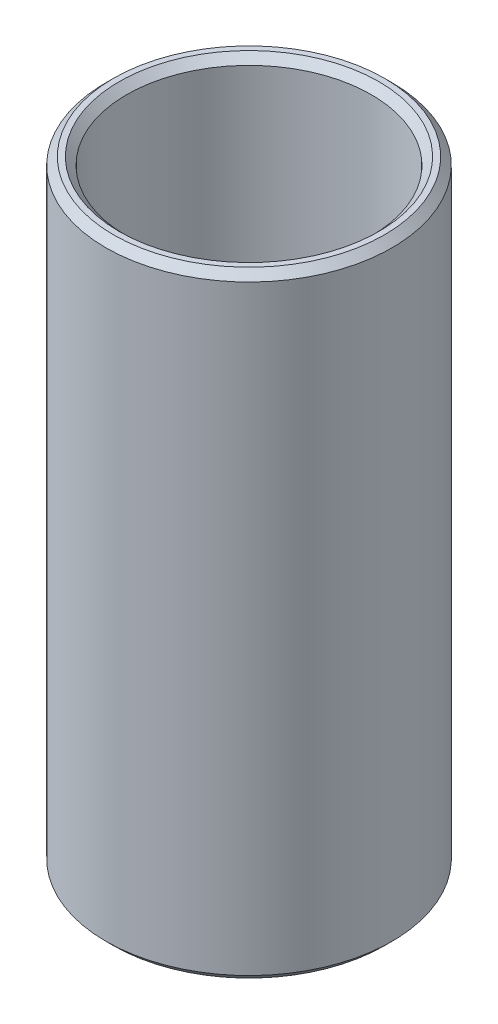
SolidWorks part; units mm, degrees
ref_plane "Front Plane" through (0, 0, 0) normal (0, 0, 1) x (1, 0, 0)
ref_plane "Top Plane" through (0, 0, 0) normal (0, 1, 0) x (1, 0, 0)
ref_plane "Right Plane" through (0, 0, 0) normal (1, 0, 0) x (0, 0, -1)
sketch "Sketch1" plane through (0, 0, 0) normal (0, 1, 0) x (1, 0, 0)
  circle A0 centre (0, 0) radius 57.5
  dimension "SLEEVE_OD" = 115
extrude "Boss-Extrude1" add sketch "Sketch1" along normal blind 247.4371
sketch "Sketch2" plane through (0, 0, 0) normal (0, 1, 0) x (1, 0, 0)
  circle A0 centre (0, 0) radius 49.1676
  dimension "BORE_D" = 98.3353
extrude "Cut-Extrude1" cut sketch "Sketch2" along normal through all
chamfer "Chamfer1" distance 3.0207 angle 45 4 edges at (0, 247.4371, 49.1676) (0, 0, 49.1676) (0, 0, 57.5) (0, 247.4371, 57.5)
